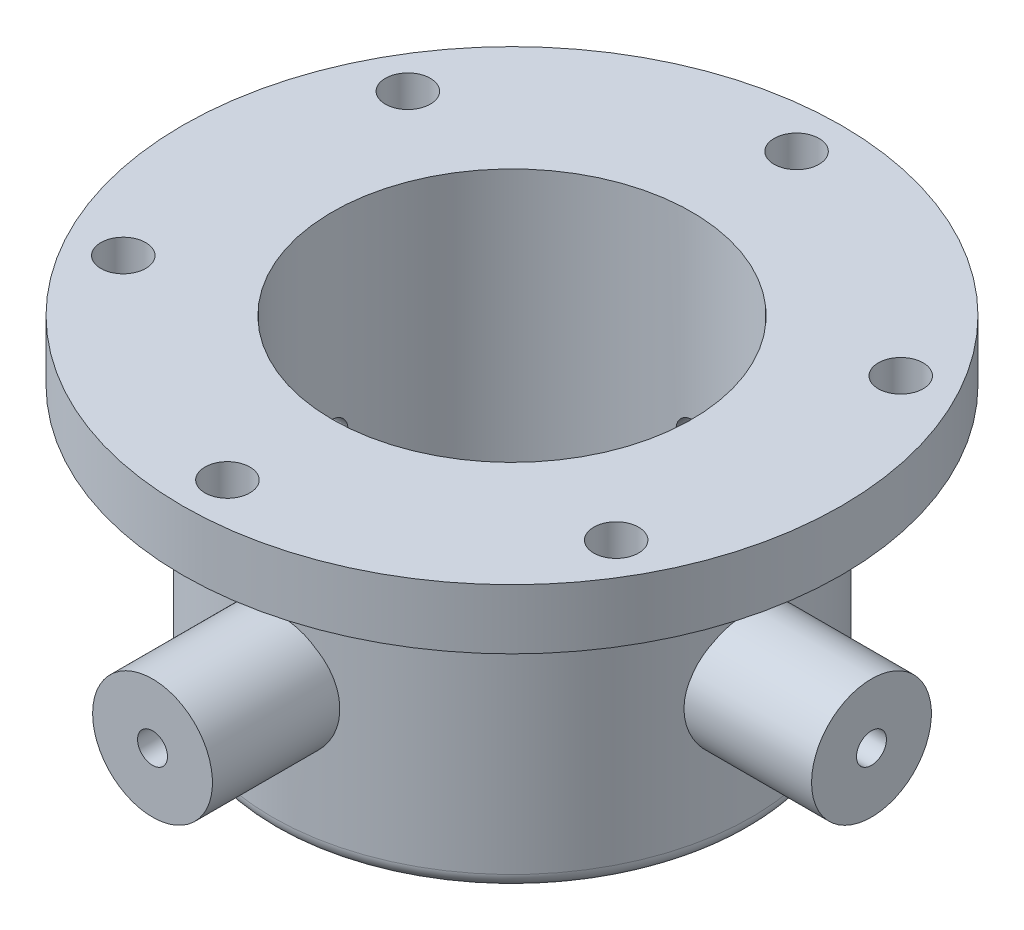
SolidWorks part; units mm, degrees
material "ABS"
ref_plane "Front Plane" through (0, 0, 0) normal (0, 0, 1) x (1, 0, 0)
ref_plane "Top Plane" through (0, 0, 0) normal (0, 1, 0) x (1, 0, 0)
ref_plane "Right Plane" through (0, 0, 0) normal (1, 0, 0) x (0, 0, -1)
sketch "Sketch1" plane through (0, 0, 0) normal (0, 1, 0) x (1, 0, 0)
  circle A0 centre (0, 0) radius 25.4
  circle A1 centre (0, 0) radius 19.05
extrude "Boss-Extrude1" add sketch "Sketch1" along normal blind 25.4
extrude "Boss-Extrude2" add sketch "Sketch1<2>" against normal blind 3.175 contours A0
sketch "Sketch1<2>" plane through (0, 0, 0) normal (0, 1, 0) x (1, 0, 0) same geometry as "Sketch1"
ref_plane "Plane3" through (19.05, 0, 0) normal (1, 0, 0) x (0, 0, -1)
sketch "Sketch2" plane through (0, 0, 0) normal (1, 0, 0) x (0, 0, -1)
  line L0 (0, 25.4) -> (0, -3.175)
  line L1 (19.05, 25.4) -> (-19.05, 25.4) construction
  line L2 (-25.4, -3.175) -> (25.4, -3.175) construction
  circle A0 centre (0, 11.1125) radius 6.35
  circle A1 centre (0, 11.1125) radius 4.7625
sketch "Sketch4" plane through (19.05, 0, 0) normal (1, 0, 0) x (0, 0, -1)
  circle A0 centre (0, 11.1125) radius 1.5875
  circle A1 centre (0, 11.1125) radius 6.35
  dimension "D1" = 3.175
extrude "Boss-Extrude3" add sketch "Sketch4" along normal blind 19.05 separate body
extrude "Cut-Extrude2" cut sketch "Sketch4<3>" against normal blind 6.35 and the other way blind 6.35 contours A0
sketch "Sketch4<3>" plane through (19.05, 0, 0) normal (1, 0, 0) x (0, 0, -1) same geometry as "Sketch4"
pattern_circular "CirPattern3" count 4 over 360 about axis through (0, 25.4, 0) along (0, 1, 0) of "Cut-Extrude2"
pattern_circular "CirPattern4" count 4 over 360 about axis through (0, 25.4, 0) along (0, 1, 0) of "Cut-Extrude2"
sketch "Sketch5" plane through (0, 25.4, 0) normal (0, 1, 0) x (1, 0, 0)
  circle A1 centre (0, 0) radius 34.925
  circle A2 centre (0, 0) radius 19.05
extrude "Boss-Extrude4" add sketch "Sketch5" along normal blind 6.35
fillet "Fillet2" radius 1.5878 2 edges at (0, -3.175, 25.4) (0, 25.4, 25.4)
sketch "Sketch7" plane through (0, 31.75, 0) normal (0, 1, 0) x (1, 0, 0)
  circle A8 centre (0, 30.1625) radius 2.3813
  circle A9 centre (26.1215, 15.0813) radius 2.3813
  circle A10 centre (26.1215, -15.0812) radius 2.3813
  circle A11 centre (0, -30.1625) radius 2.3813
  circle A12 centre (-26.1215, -15.0813) radius 2.3813
  circle A13 centre (-26.1215, 15.0812) radius 2.3813
  point P16 (0, 0)
  point P21 (2.0622, 1.1906)
  dimension "D1" = 6
  dimension "D3" = 4.7625
  dimension "D2" = 30.1625
extrude "Cut-Extrude3" cut sketch "Sketch7" against normal blind 6.35 contours A13 | A8 | A9 | A10 | A11 | A12
